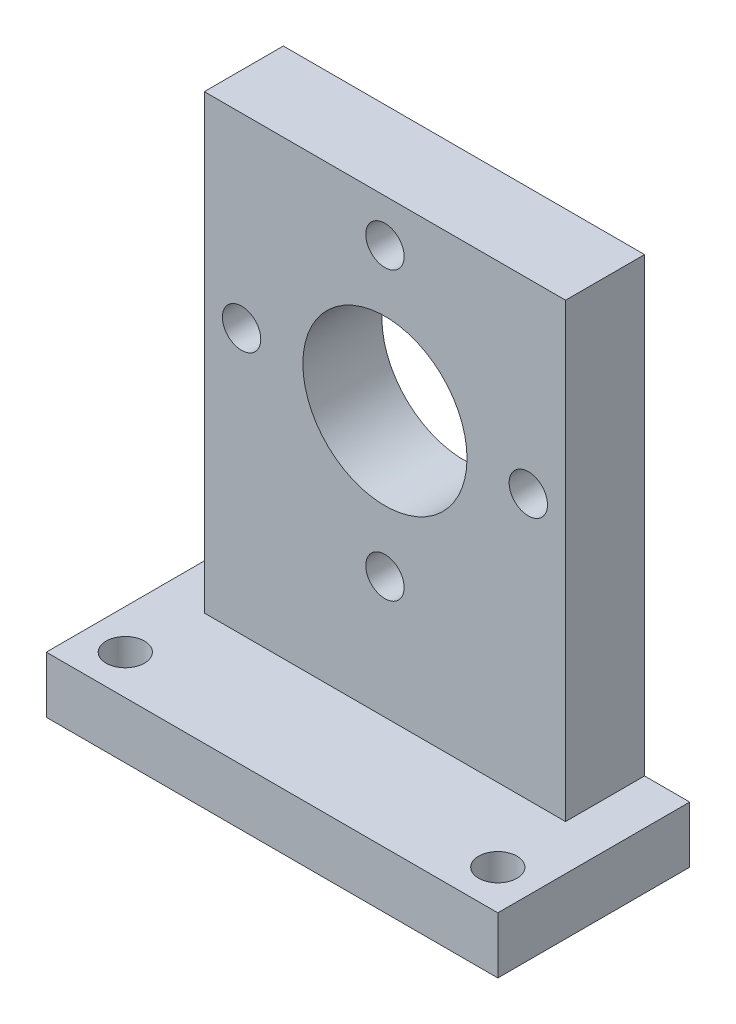
SolidWorks part; units mm, degrees
ref_plane "Front Plane" through (0, 0, 0) normal (0, 0, 1) x (1, 0, 0)
ref_plane "Top Plane" through (0, 0, 0) normal (0, 1, 0) x (1, 0, 0)
ref_plane "Right Plane" through (0, 0, 0) normal (1, 0, 0) x (0, 0, -1)
sketch "Sketch1" plane through (0, 0, 0) normal (0, 1, 0) x (1, 0, 0)
  line L1 (-20, 13.5) -> (20, 13.5)
  line L2 (-20, 13.5) -> (-20, -13.5)
  line L3 (-20, -13.5) -> (20, -13.5)
  line L4 (20, 13.5) -> (20, -13.5)
  line L5 (-20, 13.5) -> (20, -13.5) construction
  line L6 (-20, -13.5) -> (20, 13.5) construction
  line L7 (-16, 3.5) -> (16, 3.5)
  line L8 (-16, 3.5) -> (-16, -3.5)
  line L9 (-16, -3.5) -> (16, -3.5)
  line L10 (16, 3.5) -> (16, -3.5)
  line L11 (-16, 3.5) -> (16, -3.5) construction
  line L12 (-16, -3.5) -> (16, 3.5) construction
  point P0 (0, 0)
  point P6 (0, 0)
  dimension "D1" = 40
  dimension "D2" = 27
  dimension "D3" = 7
  dimension "D4" = 32
extrude "Boss-Extrude1" add sketch "Sketch1" along normal blind 5 contours L10 L7 L8 L9 | L2 L1 L4 L3 region at (0, 0, 0)
extrude "Boss-Extrude2" add sketch "Sketch1<3>" along normal blind 45 contours L10 L7 L8 L9 region at (0, 0, 0)
sketch "Sketch1<3>" plane through (0, 0, 0) normal (0, 1, 0) x (1, 0, 0) same geometry as "Sketch1"
sketch "Sketch2" plane through (0, 0, 3.5) normal (0, 0, 1) x (1, 0, 0)
  line L0 (-20, 5) -> (20, 5) construction
  circle A0 centre (0, 28.5) radius 7.2708
  dimension "D1" = 14.5415
  dimension "D2" = 23.5
extrude "Cut-Extrude1" cut sketch "Sketch2" against normal up to next
sketch "Sketch4" plane through (0, 0, 3.5) normal (0, 0, 1) x (1, 0, 0)
  line L0 (0, 45) -> (0, 28.5) construction
  line L1 (-16, 45) -> (16, 45) construction
  circle A0 centre (0, 41.2) radius 1.7
  circle A1 centre (0, 28.5) radius 7.2708 construction
  circle A2 centre (12.7, 28.5) radius 1.7
  circle A3 centre (0, 15.8) radius 1.7
  circle A4 centre (-12.7, 28.5) radius 1.7
  point P18 (0, 28.5)
  dimension "D2" = 3.4
  dimension "D1" = 12.7
  dimension "D3" = 4
extrude "Cut-Extrude2" cut sketch "Sketch4" against normal up to next
sketch "Sketch5" plane through (0, 5, 0) normal (0, 1, 0) x (1, 0, 0)
  line L1 (-20, 13.5) -> (20, 13.5) construction
  line L2 (-20, 13.5) -> (-20, -13.5) construction
  line L3 (-20, -13.5) -> (20, -13.5) construction
  line L4 (0, 13.5) -> (0, -13.5) construction
  circle A0 centre (-16.5, 10) radius 1.7
  circle A2 centre (-16.5, -10) radius 1.7
  circle A4 centre (16.5, -10) radius 1.7
  circle A5 centre (16.5, 10) radius 1.7
  dimension "D3" = 3.4
  dimension "D1" = 3.5
  dimension "D2" = 3.5
  dimension "D4" = 3.5
extrude "Cut-Extrude3" cut sketch "Sketch5" against normal up to next
sketch "Sketch7" plane through (0, 5, 0) normal (0, 1, 0) x (1, 0, 0)
  line L0 (-20, 13.5) -> (-20, -13.5) construction
  line L1 (-20, 3.5) -> (20, 3.5)
  line L2 (-20, 3.5) -> (-20, 13.5)
  line L3 (-20, 13.5) -> (20, 13.5)
  line L4 (20, 3.5) -> (20, 13.5)
  line L5 (-16, 3.5) -> (16, 3.5) construction
extrude "Cut-Extrude5" cut sketch "Sketch7" against normal up to next
sketch "Sketch8" plane through (0, 0, -3.5) normal (0, 0, -1) x (-1, 0, 0)
  line L0 (-12.7, 28.5) -> (-12.7, 2.5) construction
  line L1 (0, 0) -> (0, 13.0763) construction
  line L5 (-20, 5) -> (-20, 0) construction
  circle A0 centre (-12.7, 2.5) radius 1.7
  circle A1 centre (12.7, 2.5) radius 1.7
  circle A2 centre (-12.7, 28.5) radius 1.7 construction
  point P9 (-20, 2.5)
extrude "Cut-Extrude6" cut sketch "Sketch8" against normal blind 6.35
